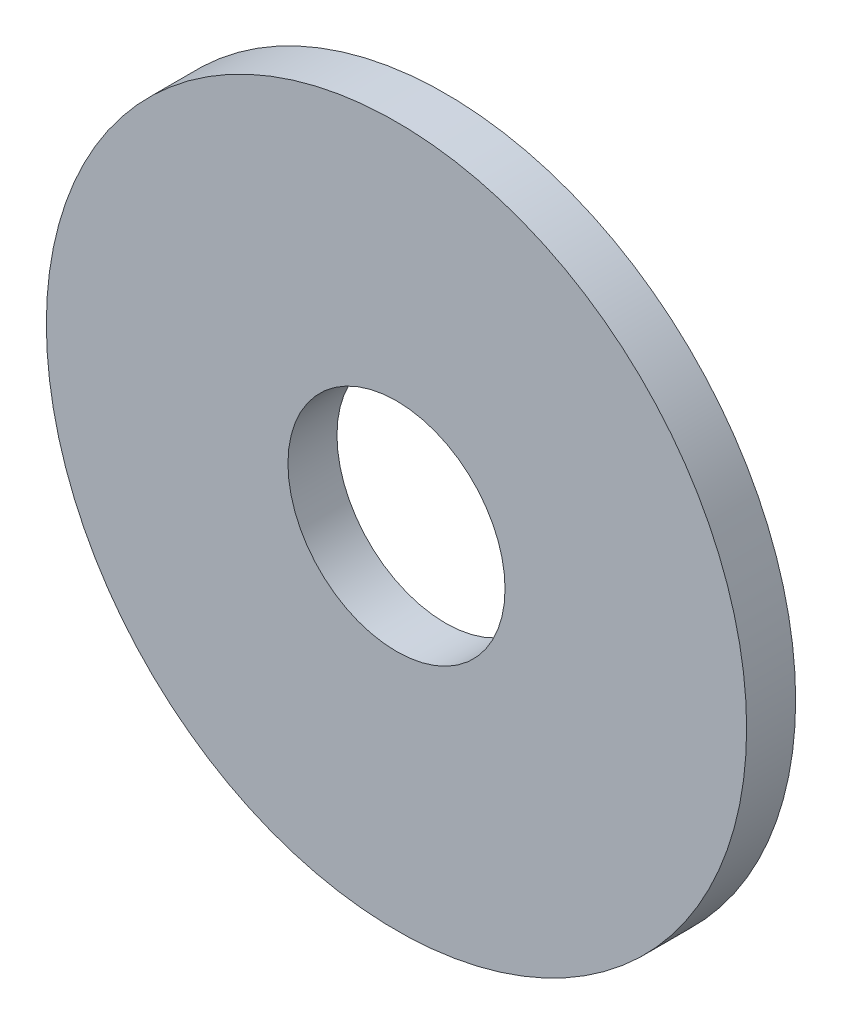
SolidWorks part; units mm, degrees
ref_plane "Front Plane" through (0, 0, 0) normal (0, 0, 1) x (1, 0, 0)
ref_plane "Top Plane" through (0, 0, 0) normal (0, 1, 0) x (1, 0, 0)
ref_plane "Right Plane" through (0, 0, 0) normal (1, 0, 0) x (0, 0, -1)
sketch "Sketch1" plane through (0, 0, 0) normal (0, 0, 1) x (1, 0, 0)
  circle A0 centre (0, 0) radius 15
  circle A1 centre (0, 0) radius 4.65
  dimension "D1" = 30
  dimension "D2" = 9.3
extrude "Boss-Extrude1" add sketch "Sketch1" along normal blind 2.1
